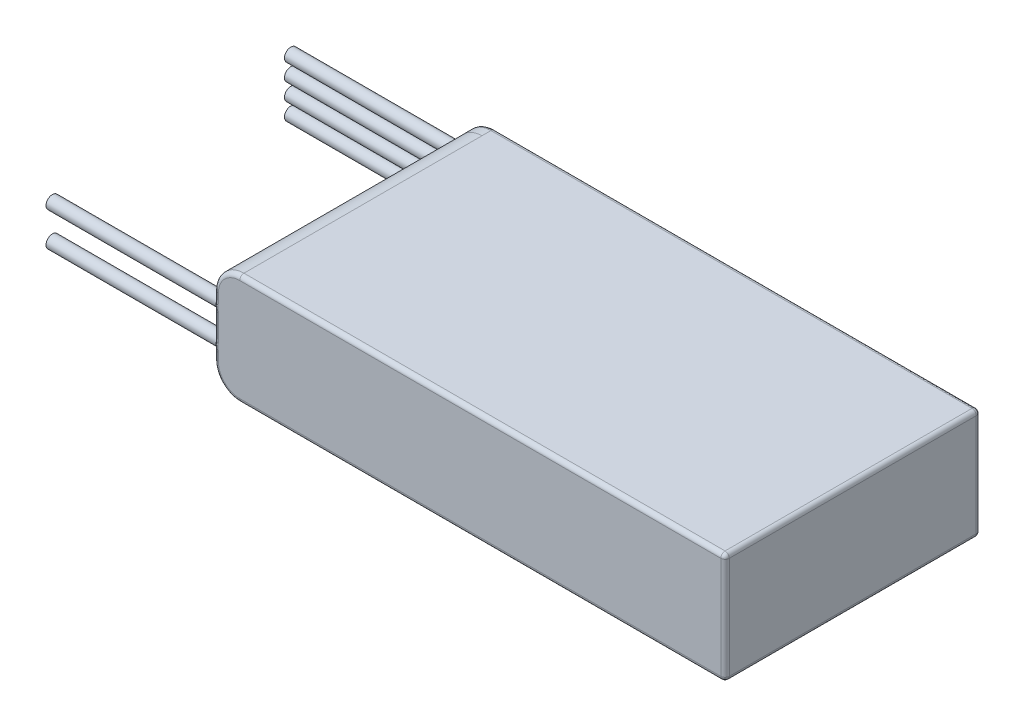
SolidWorks part; units mm, degrees
ref_plane "前视基准面" through (0, 0, 0) normal (0, 0, 1) x (1, 0, 0)
ref_plane "上视基准面" through (0, 0, 0) normal (0, 1, 0) x (1, 0, 0)
ref_plane "右视基准面" through (0, 0, 0) normal (1, 0, 0) x (0, 0, -1)
sketch "草图1" plane through (0, 0, 0) normal (0, 1, 0) x (1, 0, 0)
  line L1 (-30, 15) -> (30, 15)
  line L2 (-30, 15) -> (-30, -15)
  line L3 (-30, -15) -> (30, -15)
  line L4 (30, 15) -> (30, -15)
  line L5 (0, -15) -> (0, 15) construction
  line L6 (-30, 0) -> (30, 0) construction
  point P0 (0, 0)
  dimension "D1" = 60
  dimension "D2" = 30
extrude "凸台-拉伸1" add sketch "草图1" along normal blind 13
sketch "草图2" plane through (-30, 0, 0) normal (-1, 0, 0) x (0, 0, 1)
  line L0 (-15, 6.5) -> (15, 6.5) construction
  line L1 (-15, 13) -> (-15, 0) construction
  line L2 (15, 13) -> (15, 0) construction
  circle A0 centre (14, 8.5) radius 0.75
  circle A1 centre (-14, 7.5) radius 0.75
  circle A2 centre (-14, 9.5) radius 0.75
  circle A3 centre (14, 4.5) radius 0.75
  circle A4 centre (-14, 5.5) radius 0.75
  circle A5 centre (-14, 3.5) radius 0.75
  dimension "D1" = 1.5
  dimension "D2" = 2
  dimension "D3" = 1
  dimension "D4" = 1.5
  dimension "D5" = 1
  dimension "D6" = 1
  dimension "D7" = 1.5
  dimension "D8" = 1
  dimension "D9" = 3
extrude "凸台-拉伸2" add sketch "草图2" along normal blind 20
fillet "圆角1" radius 3 2 edges at (-30, 0, 0) (-30, 13, 0)
fillet "圆角3" radius 0.5 14 edges at (1.5, 13, 15) (-29.1213, 12.1213, 15) (-30, 6.5, 15) (-29.1213, 0.8787, 15) (1.5, 13, -15) (-29.1213, 12.1213, -15) (-30, 6.5, -15) (-29.1213, 0.8787, -15) (1.5, 0, 15) (1.5, 0, -15) (30, 13, 0) (30, 6.5, 15) (30, 6.5, -15) (30, 0, 0)
equation "\"m\"= 2"
